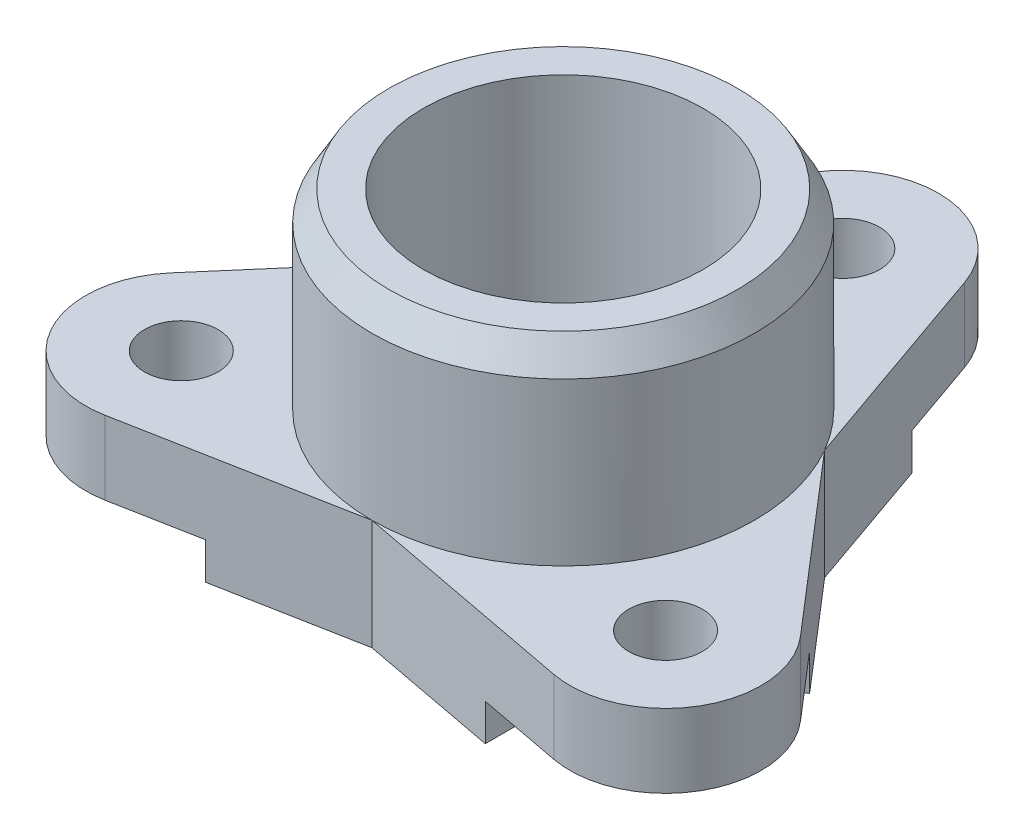
SolidWorks part; units mm, degrees
ref_plane "Front Plane" through (0, 0, 0) normal (0, 0, 1) x (1, 0, 0)
ref_plane "Top Plane" through (0, 0, 0) normal (0, 1, 0) x (1, 0, 0)
ref_plane "Right Plane" through (0, 0, 0) normal (1, 0, 0) x (0, 0, -1)
sketch "Sketch1" plane through (0, 0, 0) normal (0, 1, 0) x (1, 0, 0)
  line L1 (-13.5, -13.5) -> (13.5, -13.5)
  line L2 (-13.5, -13.5) -> (-13.5, 13.5)
  line L3 (-13.5, 13.5) -> (13.5, 13.5)
  line L4 (13.5, -13.5) -> (13.5, 13.5)
  line L5 (-13.5, -13.5) -> (13.5, 13.5) construction
  line L6 (-13.5, 13.5) -> (13.5, -13.5) construction
  line L9 (-8.2272, -4.75) -> (8.2272, 4.75) construction
  line L10 (0, 12.25) -> (0, -5.375) construction
  line L11 (-8.2272, -7.5) -> (8.2272, -7.5) construction
  line L12 (-17.497, 0) -> (23.9576, 0) construction
  line L13 (0, 9.5) -> (-8.2272, -4.75) construction
  line L14 (-8.2272, -4.75) -> (8.2272, -4.75) construction
  line L15 (8.2272, -4.75) -> (0, 9.5) construction
  line L16 (0, 12.25) -> (7.5112, 12.25) construction
  line L20 (0, 11.5) -> (-9.9593, -5.75)
  line L21 (-9.9593, -5.75) -> (9.9593, -5.75)
  line L22 (9.9593, -5.75) -> (0, 11.5)
  line L23 (0, 13) -> (-11.2583, -6.5) construction
  line L24 (-11.2583, -6.5) -> (11.2583, -6.5) construction
  line L25 (11.2583, -6.5) -> (0, 13) construction
  line L26 (-3.0678, 10.573) -> (-5.6292, 3.25)
  line L27 (-5.6292, 3.25) -> (-10.6904, -2.6298)
  line L28 (-7.6226, -7.9433) -> (0, -6.5)
  line L29 (0, -6.5) -> (7.6226, -7.9433)
  line L30 (3.0678, 10.573) -> (5.6292, 3.25)
  line L31 (5.6292, 3.25) -> (10.6904, -2.6298)
  line L32 (-4.75, -5.75) -> (-4.75, -10.8912)
  line L33 (4.75, -5.75) -> (4.75, -10.8912)
  line L34 (4.75, -10.8912) -> (-4.75, -10.8912)
  circle A0 centre (-10, 10) radius 1.5
  circle A1 centre (10, 10) radius 1.5
  circle A2 centre (10, -10) radius 1.5
  circle A3 centre (-10, -10) radius 1.5
  circle A4 centre (0, 9.5) radius 2.75
  circle A5 centre (-8.2272, -4.75) radius 2.75
  circle A6 centre (8.2272, -4.75) radius 2.75
  circle A7 centre (0, 9.5) radius 1.25
  circle A8 centre (8.2272, -4.75) radius 1.25
  circle A9 centre (-8.2272, -4.75) radius 1.25
  circle A10 centre (8.2272, 4.75) radius 1.25
  circle A11 centre (8.2272, 4.75) radius 2.75
  circle A12 centre (-8.2272, 4.75) radius 1.25
  circle A13 centre (-8.2272, 4.75) radius 2.75
  circle A14 centre (0, -9.5) radius 2.75
  circle A15 centre (0, -9.5) radius 1.25
  circle A16 centre (0, 0) radius 1.5
  circle A17 centre (0, 0) radius 9.5 construction
  circle A18 centre (0, 9.5) radius 3.25
  circle A19 centre (8.2272, -4.75) radius 3.25
  circle A20 centre (-8.2272, -4.75) radius 3.25
  circle A21 centre (0, 0) radius 4.75
  circle A22 centre (0, 0) radius 6.5
  point P0 (0, 0)
  point P14 (0, 0)
  dimension "D2" = 3
  dimension "D5" = 5.5
  dimension "D6" = 2.5
  dimension "D7" = 3
  dimension "D8" = 6.5
  dimension "D9" = 13
  dimension "D10" = 9.5
  dimension "D11" = 1
  dimension "D12" = 0.75
  dimension "D1" = 27
  dimension "D3" = 10
  dimension "D4" = 19.75
  dimension "D13" = 9.5
  dimension "D14" = 4.75
extrude "Boss-Extrude1" add sketch "Sketch1" along normal blind 2.5 contours L22 A18 L20 A4 | A22 L20 A18 L26 | A22 L27 A20 L20 | A20 L21 A5 L20 | A22 A20 L20 A5 L21 | A22 L20 A20 | A9 L21 A5 L20 | A9 L20 A5 L21 | A20 A22 | L20 A22 | L21 A22 A19 L22 A18 L20 A20 A21 | A22 A18 L20 | A22 A18 L22 A4 L20 | A18 A22 | A22 L22 A18 | A22 L30 A18 L22 | L22 A22 | A22 L22 A19 L31 | A22 A19 L22 | A22 A19 L21 A6 L22 | A19 L22 A6 L21 | A19 A22 | A8 L22 A6 L21 | A8 L22 L21 A6 | A8 L21 L22 | A22 L21 A19 | A22 A20 L21 | A9 L20 L21 | A7 L22 L20 | A7 L22 A4 L20 | A7 L20 A4 L22 | A22 L29 L33 L21 | A19 L21 L33 L29 | A22 L21 L32 L28 | A20 L28 L32 L21 | A22 L21 region at (0, 0, -10.9789) region at (-0.3069, 0, -11.1102) region at (0, 0, -7.8131) region at (0, 0, -6.6999) region at (-2.3529, 0, -7.5941) region at (-2.3556, 0, -6.4442) region at (-3.7952, 0, -6.6786) region at (3.7952, 0, -6.6786) region at (2.3556, 0, -6.4442) region at (-2.2309, 0, -5.9152) region at (-5.2408, 0, -3.0258) region at (0, 0, -6.3834) region at (5.2408, 0, -3.0258) region at (-6.7586, 0, 1.1821) region at (-7.6814, 0, 0.0525) region at (7.6814, 0, 0.0525) region at (6.7586, 0, 1.1821) region at (-6.7849, 0, 1.894) region at (-7.7584, 0, 1.7563) region at (-5.5282, 0, 3.1917) region at (9.2349, 0, 1.7558) region at (7.636, 0, 1.827) region at (-6.7664, 0, 3.9066) region at (-8.3316, 0, 2.7777) region at (-4.403, 0, 5.2621) region at (-5.421, 0, 6.9268) region at (9.9693, 0, 2.7219) region at (6.7664, 0, 3.9066) region at (5.5282, 0, 3.1917) region at (-3.2337, 0, 6.4982) region at (0, 0, 6.0515) region at (4.403, 0, 5.2621) region at (5.421, 0, 6.9268) region at (-9.508, 0, 5.4895) region at (3.2337, 0, 6.4982) region at (9.508, 0, 5.4895)
extrude "Boss-Extrude2" add sketch "Sketch1<9>" along normal blind 9 contours L21 A22 A19 L22 A18 L20 A20 A21 | A22 L21 | A20 A22 | L20 A22 | L22 A22 | A19 A22 | A18 A22 region at (-2.2309, 0, -5.9152) region at (-5.2408, 0, -3.0258) region at (0, 0, -6.3834) region at (5.2408, 0, -3.0258) region at (-5.5282, 0, 3.1917) region at (5.5282, 0, 3.1917) region at (0, 0, 6.0515)
sketch "Sketch1<9>" plane through (0, 0, 0) normal (0, 1, 0) x (1, 0, 0) same geometry as "Sketch1"
chamfer "Chamfer1" distance 1 angle 30 1 edges at (0, 9, 6.5) first distance on face at (0, 2.5, 0)
extrude "Boss-Extrude3" add sketch "Sketch1<10>" against normal blind 1.25 contours A22 L21 L32 L28 | A22 L21 | A22 L29 L33 L21 region at (-3.2337, 0, 6.4982) region at (0, 0, 6.0515) region at (3.2337, 0, 6.4982)
sketch "Sketch1<10>" plane through (0, 0, 0) normal (0, 1, 0) x (1, 0, 0) same geometry as "Sketch1"
pattern_circular "CirPattern1" count 3 over 360 about axis through (0, 2.5, 0) along (0, -1, 0) of "Boss-Extrude3" reverse direction yes
